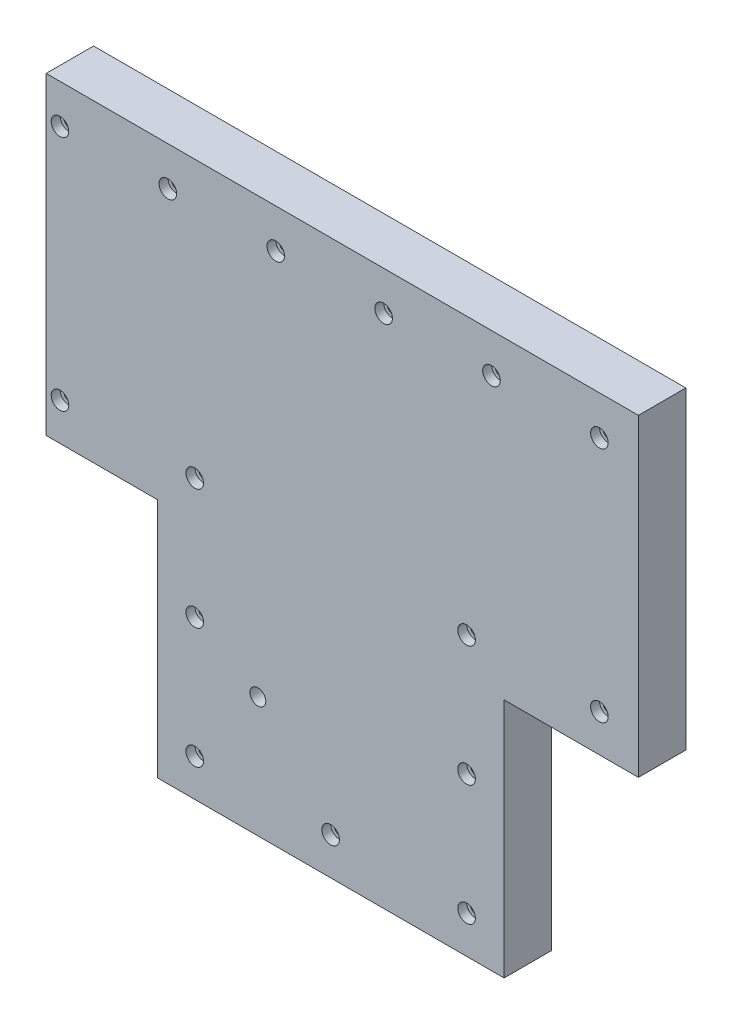
SolidWorks part; units mm, degrees
ref_plane "Front Plane" through (0, 0, 0) normal (0, 0, 1) x (1, 0, 0)
ref_plane "Top Plane" through (0, 0, 0) normal (0, 1, 0) x (1, 0, 0)
ref_plane "Right Plane" through (0, 0, 0) normal (1, 0, 0) x (0, 0, -1)
sketch "Sketch10" plane through (0, 0, 0) normal (0, 0, 1) x (1, 0, 0)
  line L0 (0, 10) -> (0, 0)
  line L1 (170, 0) -> (170, 10) construction
  line L2 (170, 0) -> (180, 0) construction
  line L3 (170, -65) -> (180, -65) construction
  line L4 (0, 0) -> (170, 0)
  line L5 (170, 0) -> (170, -65)
  line L6 (170, -65) -> (128, -65)
  line L7 (128, -65) -> (128, -141.2)
  line L8 (128, -141.2) -> (52, -141.2)
  line L9 (52, -141.2) -> (52, -65)
  line L10 (170, -65) -> (170, -75) construction
  line L11 (52, -65) -> (0, -65)
  line L12 (0, -65) -> (0, -75)
  line L13 (138, -75) -> (138, -65) construction
  line L14 (0, -75) -> (42, -75)
  line L15 (42, -75) -> (42, -151.2)
  line L16 (42, -151.2) -> (138, -151.2)
  line L17 (138, -151.2) -> (138, -75)
  line L18 (138, -75) -> (180, -75)
  line L19 (138, -75) -> (128, -75) construction
  line L20 (128, -141.2) -> (138, -141.2) construction
  line L21 (180, -75) -> (180, 10)
  line L22 (180, 10) -> (0, 10)
  line L23 (0, 10) -> (0, 13.175)
  line L24 (128, -141.2) -> (128, -151.2) construction
  line L25 (0, 13.175) -> (183.175, 13.175)
  line L26 (183.175, 13.175) -> (183.175, -78.175)
  line L27 (183.175, -78.175) -> (141.175, -78.175)
  line L28 (141.175, -78.175) -> (141.175, -154.375)
  line L29 (141.175, -154.375) -> (38.825, -154.375)
  line L30 (38.825, -154.375) -> (38.825, -78.175)
  line L31 (38.825, -78.175) -> (0, -78.175)
  line L32 (52, -141.2) -> (52, -151.2) construction
  line L33 (0, -78.175) -> (0, -75)
  line L34 (64.1463, -2) -> (57.0752, -2)
  line L35 (57.0752, -2) -> (55.0752, 0)
  line L36 (55.0752, 0) -> (62.1463, 0)
  line L37 (62.1463, 0) -> (64.1463, -2)
  line L38 (64.9747, 0) -> (66.9747, -2)
  line L39 (66.9747, -2) -> (74.0458, -2)
  line L40 (74.0458, -2) -> (72.0458, 0)
  line L41 (72.0458, 0) -> (64.9747, 0)
  line L42 (128, -65) -> (120.0752, -65)
  line L43 (64.1463, -2) -> (127.1463, -65)
  line L44 (55.0752, 0) -> (55.0752, -10.3495) construction
  line L45 (120.0752, -65) -> (57.0752, -2)
  line L46 (0, 0) -> (0, -65)
  line L47 (127.1463, -65) -> (129.9747, -65)
  line L48 (129.9747, -65) -> (127.9747, -63)
  line L49 (127.9747, -63) -> (66.9747, -2)
  line L50 (74.0458, -2) -> (135.0458, -63)
  line L51 (135.0458, -63) -> (137.0458, -65)
  line L52 (137.0458, -65) -> (128, -65)
  line L55 (135.0458, -63) -> (127.9747, -63)
  line L56 (52, -141.2) -> (42, -141.2) construction
  line L57 (42, -75) -> (52, -75) construction
  line L58 (42, -75) -> (42, -65) construction
  line L59 (4.3688, 5) -> (38.495, 5) construction
  line L60 (38.495, 5) -> (72.6213, 5) construction
  line L61 (72.6213, 5) -> (106.7475, 5) construction
  line L62 (106.7475, 5) -> (140.8738, 5) construction
  line L63 (140.8738, 5) -> (175, 5) construction
  line L64 (180, 10) -> (183.175, 13.175) construction
  line L65 (138, -75) -> (141.175, -78.175) construction
  line L66 (180, -75) -> (183.175, -78.175) construction
  line L67 (138, -151.2) -> (141.175, -154.375) construction
  line L68 (42, -151.2) -> (38.825, -154.375) construction
  line L69 (42, -75) -> (38.825, -78.175) construction
  line L70 (4.3688, -70) -> (47, -70) construction
  line L71 (133, -70) -> (175, -70) construction
  line L72 (47, -70) -> (47, -108.1) construction
  line L73 (47, -108.1) -> (47, -146.2) construction
  line L74 (47, -146.2) -> (90, -146.2) construction
  line L75 (90, -146.2) -> (133, -146.2) construction
  line L76 (133, -146.2) -> (133, -108.1) construction
  line L77 (133, -108.1) -> (133, -70) construction
  circle A0 centre (4.3688, 5) radius 3.175 construction
  circle A1 centre (38.495, 5) radius 3.175 construction
  circle A2 centre (72.6213, 5) radius 3.175 construction
  circle A3 centre (106.7475, 5) radius 3.175 construction
  circle A4 centre (140.8738, 5) radius 3.175 construction
  circle A5 centre (175, 5) radius 3.175 construction
  circle A6 centre (175, -70) radius 3.175 construction
  circle A7 centre (133, -70) radius 3.175 construction
  circle A8 centre (133, -108.1) radius 3.175 construction
  circle A9 centre (133, -146.2) radius 3.175 construction
  circle A10 centre (90, -146.2) radius 3.175 construction
  circle A11 centre (47, -146.2) radius 3.175 construction
  circle A12 centre (47, -108.1) radius 3.175 construction
  circle A13 centre (47, -70) radius 3.175 construction
  circle A14 centre (4.3688, -70) radius 3.175 construction
  circle A15 centre (66.9747, -119.9778) radius 2.5
  dimension "D1" = 6.35
  dimension "D15" = 5
  dimension "D2" = 170
  dimension "D3" = 10
  dimension "D4" = 5
  dimension "D5" = 4.3688
  dimension "D6" = 3.175
  dimension "D7" = 3.175
  dimension "D8" = 5
  dimension "D9" = 76.2
  dimension "D10" = 76
  dimension "D11" = 76.2
  dimension "D12" = 86
  dimension "D13" = 5
  dimension "D14" = 5
  dimension "D16" = 65
  dimension "D17" = 5
  dimension "D18" = 52
  dimension "D19" = 55.0752
  dimension "D20" = 2
  dimension "D21" = 2
  dimension "D22" = 7.0711
  dimension "D23" = 2
  dimension "D24" = 45
extrude "Boss-Extrude2" add sketch "Sketch10" along normal blind 6.35 contours L4 L46 L11 L9 L8 L7 L42 L45 L35 | L50 L51 L42 L6 L5 L4 L40 | L21 L22 L0 L4 L5 L6 L7 L8 L9 L11 L12 L14 L15 L16 L17 L18 | L55 L50 L39 L49 | L45 L42 L43 L34 | L48 L49 L38 L4 L37 L43 L42 | L51 L55 L48 L42 | L37 L4 L35 L34 | L39 L40 L4 L38 | L33 L31 L30 L29 L28 L27 L26 L25 L23 L22 L21 L18 L17 L16 L15 L14 region at (90, 7.5837, 0) region at (2.4825, 11.5875, 0) region at (68.091, -70.0112, 0) region at (59.6107, -1, 0) region at (96.0605, -32.5, 0) region at (92.1107, -33.5, 0) region at (69.5102, -1, 0) region at (134.5833, -27.1209, 0) region at (101.0102, -32.5, 0) region at (132.5102, -64, 0)
hole_wizard "CBORE for #4 Socket Head Cap Screw1" positions "3DSketch2" profile "Sketch12" counterbore size "#4" standard "ANSI Inch" end condition through all
sketch3d "3DSketch2"
  point P0 (4.3688, 5, 6.35)
  point P5 (38.495, 5, 6.35)
  point P7 (72.6213, 5, 6.35)
  point P9 (106.7475, 5, 6.35)
  point P11 (140.8738, 5, 6.35)
  point P13 (175, 5, 6.35)
  point P15 (175, -70, 6.35)
  point P17 (133, -70, 6.35)
  point P19 (133, -108.1, 6.35)
  point P21 (133, -146.2, 6.35)
  point P23 (90, -146.2, 6.35)
  point P25 (47, -146.2, 6.35)
  point P27 (47, -108.1, 6.35)
  point P29 (47, -70, 6.35)
  point P31 (4.3688, -70, 6.35)
sketch "Sketch12" plane through (4.3688, 5, 6.35) normal (1, 0, 0) x (0, -1, 0)
  line L0 (0, 0) -> (0, 6.35)
  line L1 (0, 6.35) -> (1.6319, 6.35)
  line L3 (1.6319, 6.35) -> (1.6319, 2.8448)
  line L4 (1.6319, 2.8448) -> (2.7788, 2.8448)
  line L5 (2.7788, 2.8448) -> (2.7788, 0)
  line L7 (2.7788, 0) -> (0, 0)
  line L11 (0, -6.35) -> (0, 107.95) construction
  dimension "Thru Hole Dia." = 3.2639
  dimension "Thru Hole Depth" = 6.35
  dimension "C'Bore Dia." = 5.5575
  dimension "C'Bore Depth" = 2.8448
sketch "Sketch13" plane through (0, 0, 0) normal (0, 0, 1) x (1, 0, 0)
  line L9 (0, -75) -> (0, -78.175)
  line L10 (0, -78.175) -> (0, -78.675)
  line L11 (0, -78.675) -> (38.325, -78.675)
  line L12 (38.325, -78.675) -> (38.325, -154.875)
  line L13 (38.325, -154.875) -> (141.675, -154.875)
  line L14 (0, -78.175) -> (38.825, -78.175)
  line L15 (141.675, -154.875) -> (141.675, -78.675)
  line L16 (38.825, -78.175) -> (38.825, -154.375)
  line L17 (141.675, -78.675) -> (183.675, -78.675)
  line L18 (183.675, -78.675) -> (183.675, 13.675)
  line L19 (183.675, 13.675) -> (0, 13.675)
  line L20 (0, 13.675) -> (0, 13.175)
  line L21 (183.175, 13.175) -> (183.175, 13.675) construction
  line L22 (38.825, -154.375) -> (141.175, -154.375)
  line L23 (183.175, 13.175) -> (183.675, 13.175) construction
  line L24 (141.175, -154.375) -> (141.175, -78.175)
  line L29 (141.175, -78.175) -> (183.175, -78.175)
  line L35 (183.175, -78.175) -> (183.175, 13.175)
  line L36 (183.175, -78.175) -> (183.675, -78.175) construction
  line L37 (183.175, -78.175) -> (183.175, -78.675) construction
  line L38 (141.675, -78.675) -> (141.675, -78.175) construction
  line L39 (183.175, -78.175) -> (141.175, -78.175) construction
  line L40 (141.675, -78.675) -> (141.175, -78.675) construction
  line L41 (141.175, -78.175) -> (141.175, -154.375) construction
  line L42 (141.175, -154.375) -> (141.675, -154.375) construction
  line L43 (141.175, -154.375) -> (141.175, -154.875) construction
  line L44 (38.825, -154.375) -> (38.825, -154.875) construction
  line L45 (38.825, -154.375) -> (38.325, -154.375) construction
  line L46 (38.325, -78.675) -> (38.325, -78.175) construction
  line L47 (38.825, -78.175) -> (0, -78.175) construction
  line L48 (38.325, -78.675) -> (38.825, -78.675) construction
  line L49 (38.825, -154.375) -> (38.825, -78.175) construction
  line L50 (0, -78.675) -> (0, -81.85)
  line L51 (0, -81.85) -> (35.15, -81.85)
  line L52 (35.15, -81.85) -> (35.15, -158.05)
  line L53 (35.15, -158.05) -> (144.85, -158.05)
  line L54 (144.85, -158.05) -> (144.85, -81.85)
  line L55 (144.85, -81.85) -> (187.35, -81.85)
  line L56 (187.35, -81.85) -> (187.35, 17.35)
  line L57 (187.35, 17.35) -> (0, 17.35)
  line L58 (0, 17.35) -> (0, 13.675)
  line L59 (183.175, 13.675) -> (183.175, 17.35) construction
  line L60 (183.675, 13.175) -> (187.35, 13.175) construction
  line L61 (183.675, -78.175) -> (187.35, -78.175) construction
  line L62 (183.175, -78.675) -> (183.175, -81.85) construction
  line L63 (144.85, -81.85) -> (144.85, -78.175) construction
  line L64 (144.85, -81.85) -> (141.175, -81.85) construction
  line L65 (141.675, -154.375) -> (144.85, -154.375) construction
  line L66 (141.175, -154.875) -> (141.175, -158.05) construction
  line L67 (38.825, -154.875) -> (38.825, -158.05) construction
  line L68 (38.325, -154.375) -> (35.15, -154.375) construction
  line L69 (35.15, -81.85) -> (35.15, -78.675) construction
  line L70 (35.15, -81.85) -> (38.325, -81.85) construction
  line L71 (183.175, 13.175) -> (0, 13.175)
  line L72 (0, 10) -> (0, 13.175)
  line L73 (0, -75) -> (42, -75)
  line L74 (42, -75) -> (42, -151.2)
  line L75 (42, -151.2) -> (138, -151.2)
  line L76 (138, -75) -> (180, -75)
  line L77 (180, -75) -> (180, 10)
  line L78 (180, 10) -> (0, 10)
  line L79 (138, -75) -> (180, -75) construction
  line L80 (138, -75) -> (138, -151.2)
  dimension "D1" = 0.5
  dimension "D2" = 3.175
extrude "Boss-Extrude3" add sketch "Sketch13" against normal blind 15 from surface separate body contours L57 L58 L19 L18 L17 L15 L13 L12 L11 L50 L51 L52 L53 L54 L55 L56 region at (19.1625, -81.2414, 0) starting at face at (7.1476, 5, 6.35)
extrude "Boss-Extrude6" add sketch "Sketch13<7>" against normal blind 3.175 from surface contours L76 L80 L75 L74 L73 L9 L14 L16 L22 L24 L29 L35 L71 L72 L78 L77 | L71 L35 L29 L24 L22 L16 L14 L10 L11 L12 L13 L15 L17 L18 L19 L20 region at (21, -77.4825, 0) region at (19.4125, -78.4243, 0) starting at face at (7.1476, 5, 6.35)
sketch "Sketch13<7>" plane through (0, 0, 0) normal (0, 0, 1) x (1, 0, 0) same geometry as "Sketch13"
